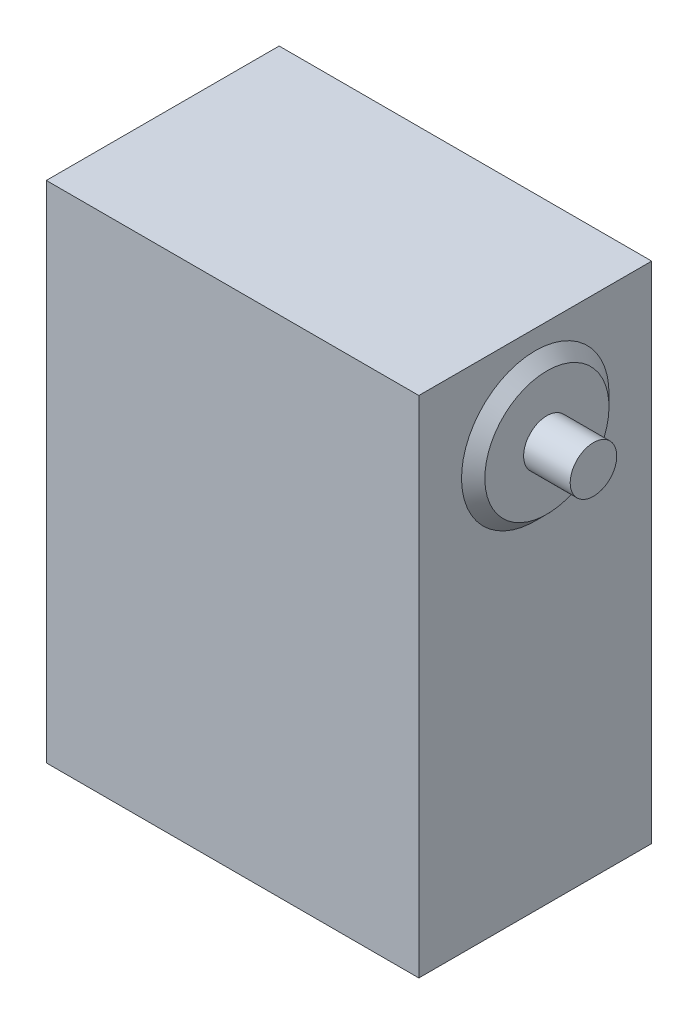
SolidWorks part; units mm, degrees
ref_plane "Front Plane" through (0, 0, 0) normal (0, 0, 1) x (1, 0, 0)
ref_plane "Top Plane" through (0, 0, 0) normal (0, 1, 0) x (1, 0, 0)
ref_plane "Right Plane" through (0, 0, 0) normal (1, 0, 0) x (0, 0, -1)
sketch "Sketch1" plane through (0, 0, 0) normal (0, 0, 1) x (1, 0, 0)
  line L0 (-113.25, 0) -> (116.4643, 0) construction
  line L2 (-24, -32.5) -> (24, -32.5)
  line L3 (-24, -32.5) -> (-24, 32.5)
  line L4 (-24, 32.5) -> (24, 32.5)
  line L5 (24, -32.5) -> (24, 32.5)
  point P7 (0, 32.5)
  point P8 (24, 0)
  dimension "D1" = 48
  dimension "D2" = 65
extrude "Boss-Extrude1" add sketch "Sketch1" along normal blind 15 and the other way blind 15
sketch "Sketch2" plane through (-24, 0, 0) normal (-1, 0, 0) x (0, 0, 1)
  line L0 (12, 29.5) -> (-12, 29.5) construction
  line L1 (-12, 29.5) -> (-12, 5.5) construction
  line L2 (-12, 5.5) -> (-12, -29.5) construction
  line L3 (-12, -29.5) -> (12, -29.5) construction
  line L4 (12, -29.5) -> (12, 5.5) construction
  line L5 (12, 5.5) -> (12, 29.5) construction
  line L6 (0, 29.5) -> (0, 32.5) construction
  line L7 (0, 32.5) -> (16.6874, 32.5) construction
  line L8 (-15, 32.5) -> (15, 32.5) construction
  circle A0 centre (-12, 29.5) radius 1.25
  circle A1 centre (12, 29.5) radius 1.25
  circle A2 centre (12, 5.5) radius 1.25
  circle A3 centre (-12, 5.5) radius 1.25
  circle A4 centre (-12, -29.5) radius 1.25
  circle A5 centre (12, -29.5) radius 1.25
  dimension "D1" = 2.5
  dimension "D2" = 2.5
  dimension "D3" = 2.5
  dimension "D4" = 2.5
  dimension "D5" = 2.5
  dimension "D6" = 2.5
extrude "Cut-Extrude1" cut sketch "Sketch2" against normal blind 10
sketch "Sketch4" plane through (-24, 0, 0) normal (-1, 0, 0) x (0, 0, 1)
  line L0 (0, 20.5) -> (0, 32.5) construction
  line L1 (-15, 32.5) -> (15, 32.5) construction
  circle A0 centre (0, 20.5) radius 9.5
  circle A1 centre (0, 20.5) radius 8
  circle A2 centre (0, 20.5) radius 3
  point P7 (0, 32.5)
extrude "Boss-Extrude3" add sketch "Sketch4" along normal blind 1.5 contours A0 A1 | A1 A2 | A2 region at (-24, 20.5, -9.2313) region at (-24, 20.5, -7.7737) region at (-24, 20.5, 0)
chamfer "Chamfer2" distance 1.5 angle 45 1 edges at (-25.5, 11, 0)
sketch "Sketch5" plane through (-25.5, 0, 0) normal (-1, 0, 0) x (0, 0, 1)
  circle A0 centre (0, 20.5) radius 3
extrude "Boss-Extrude4" add sketch "Sketch5" along normal blind 6
mirror "Mirror1" about plane through (0, 0, 0) normal (1, 0, 0) of "Boss-Extrude4", "Chamfer2", "Boss-Extrude3"
